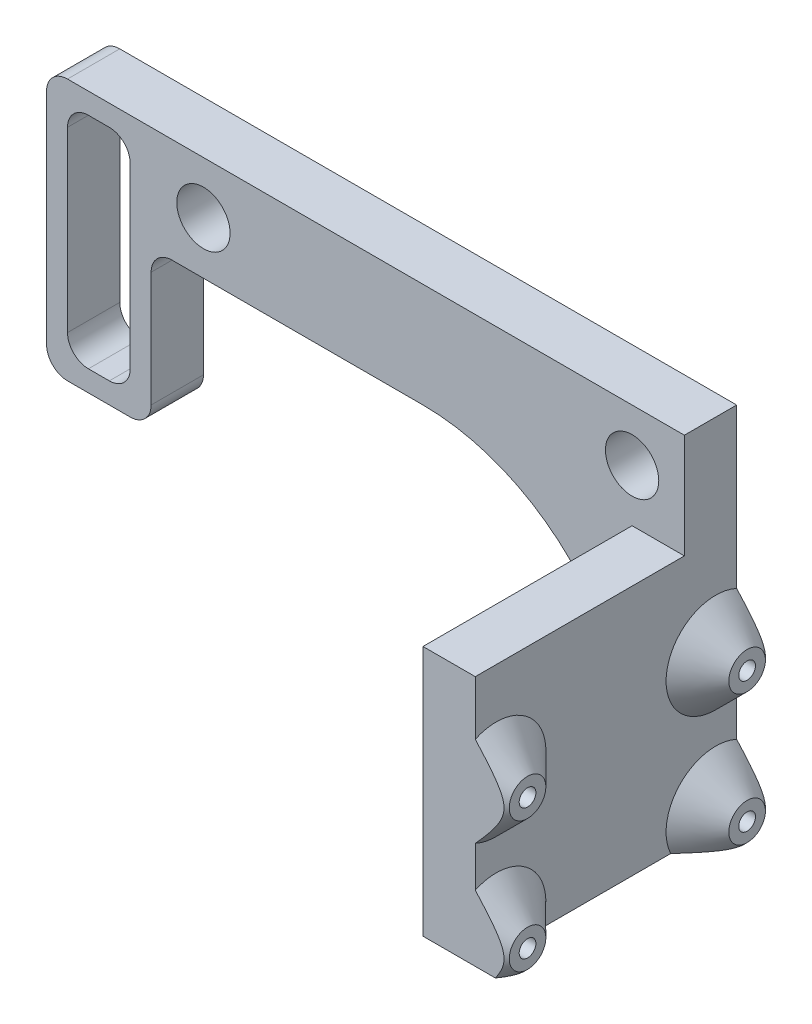
SolidWorks part; units mm, degrees
ref_plane "Front Plane" through (0, 0, 0) normal (0, 0, 1) x (1, 0, 0)
ref_plane "Top Plane" through (0, 0, 0) normal (0, 1, 0) x (1, 0, 0)
ref_plane "Right Plane" through (0, 0, 0) normal (1, 0, 0) x (0, 0, -1)
sketch "Sketch1" plane through (0, 0, 0) normal (0, 0, 1) x (1, 0, 0)
  line L0 (0, 5) -> (51, 5) construction
  line L1 (0, 0) -> (51, 0)
  line L2 (0, 0) -> (0, 10)
  line L3 (0, 10) -> (51, 10)
  line L4 (51, 0) -> (51, 10)
  circle A0 centre (5, 5) radius 2.55
  circle A1 centre (46, 5) radius 2.55
  dimension "D5" = 5.1
  dimension "D1" = 10
  dimension "D2" = 41
  dimension "D3" = 5
  dimension "D4" = 5
extrude "Boss-Extrude1" add sketch "Sketch1" along normal blind 5
sketch "Sketch3" plane through (0, 0, 5) normal (0, 0, 1) x (1, 0, 0)
  line L0 (-2, -13) -> (-8, -13)
  line L1 (0, 10) -> (-10, 10)
  line L2 (0, 10) -> (0, -15)
  line L3 (0, -15) -> (-10, -15)
  line L4 (-10, 10) -> (-10, -15)
  line L5 (-8, 8) -> (-8, -13)
  line L6 (-2, 8) -> (-8, 8)
  line L7 (-2, 8) -> (-2, -13)
  dimension "D1" = 10
  dimension "D2" = 25
  dimension "D3" = 2
extrude "Boss-Extrude2" add sketch "Sketch3" against normal up to surface (5 mm away) up to face at (7.55, 5, 0)
sketch "Sketch5" plane through (51, 0, 0) normal (1, 0, 0) x (0, 0, -1)
  line L1 (0, 0) -> (-25, 0)
  line L2 (0, 0) -> (0, -24)
  line L3 (0, -24) -> (-25, -24)
  line L4 (-25, 0) -> (-25, -24)
  dimension "D1" = 24
  dimension "D2" = 25
extrude "Boss-Extrude3" add sketch "Sketch5" against normal blind 5
fillet "Fillet1" radius 20 1 edges at (46, 0, 2.5)
sketch "Sketch6" plane through (51, 0, 0) normal (1, 0, 0) x (0, 0, -1)
  line L0 (-25, -24) -> (0, -24) construction
  line L1 (-23, -22) -> (-2, -22) construction
  line L2 (-23, -22) -> (-23, -9.5) construction
  line L3 (-23, -9.5) -> (-2, -9.5) construction
  line L4 (-2, -22) -> (-2, -9.5) construction
  line L5 (-25, 0) -> (-25, -24) construction
  circle A0 centre (-23, -9.5) radius 1.75
  circle A1 centre (-23, -22) radius 1.75
  circle A2 centre (-2, -22) radius 1.75
  circle A3 centre (-2, -9.5) radius 1.75
  dimension "D5" = 3.5
  dimension "D1" = 2
  dimension "D2" = 2
  dimension "D3" = 21
  dimension "D4" = 12.5
extrude "Boss-Extrude4" add sketch "Sketch6" along normal blind 3
chamfer "Chamfer1" distance 3 angle 45 4 edges at (51, -9.5, 3.75) (51, -22, 3.75) (51, -22, 24.75) (51, -9.5, 24.75)
hole_wizard "M2x0.4 Tapped Hole1" positions "Sketch7" profile "Sketch8" tap size "M2x0.4" standard "ANSI Metric"
sketch "Sketch7" plane through (54, 0, 0) normal (1, 0, 0) x (0, 0, -1)
  circle A0 centre (-2, -22) radius 1.75 construction
  circle A1 centre (-23, -22) radius 1.75 construction
  circle A2 centre (-23, -9.5) radius 1.75 construction
  circle A3 centre (-2, -9.5) radius 1.75 construction
  point P0 (-23, -22)
  point P2 (-23, -9.5)
  point P4 (-2, -9.5)
  point P6 (-2, -22)
  point P11 (0, 0)
  point P14 (0, 0)
  point P15 (0, 0)
  point P20 (0, 0)
cosmetic thread "Hole Thread1" parameters "D2"=2
cosmetic thread "Hole Thread2" parameters "D2"=2
cosmetic thread "Hole Thread3" parameters "D2"=2
cosmetic thread "Hole Thread4" parameters "D2"=2
sketch "Sketch8" plane through (54, -22, 23) normal (0, 1, 0) x (0, 0, -1)
  line L0 (0, 0) -> (0, 9.6807)
  line L1 (0, 9.6807) -> (0.8, 9.2)
  line L2 (0.8, 9.2) -> (0.8, 0)
  line L5 (0.8, 0) -> (0, 0)
  line L10 (0, 9.6807) -> (-0.8, 9.2) construction
  line L11 (0, -6.35) -> (0, 107.95) construction
  dimension "Tap Drill Dia." = 1.6
  dimension "Tap Drill Depth" = 9.2
  dimension "Drill Angle" = 118
fillet "Fillet2" radius 2 8 edges at (-8, -13, 2.5) (-2, -13, 2.5) (-8, 8, 2.5) (-2, 8, 2.5) (-10, 10, 2.5) (-10, -15, 2.5) (0, -15, 2.5) (0, 0, 2.5)
